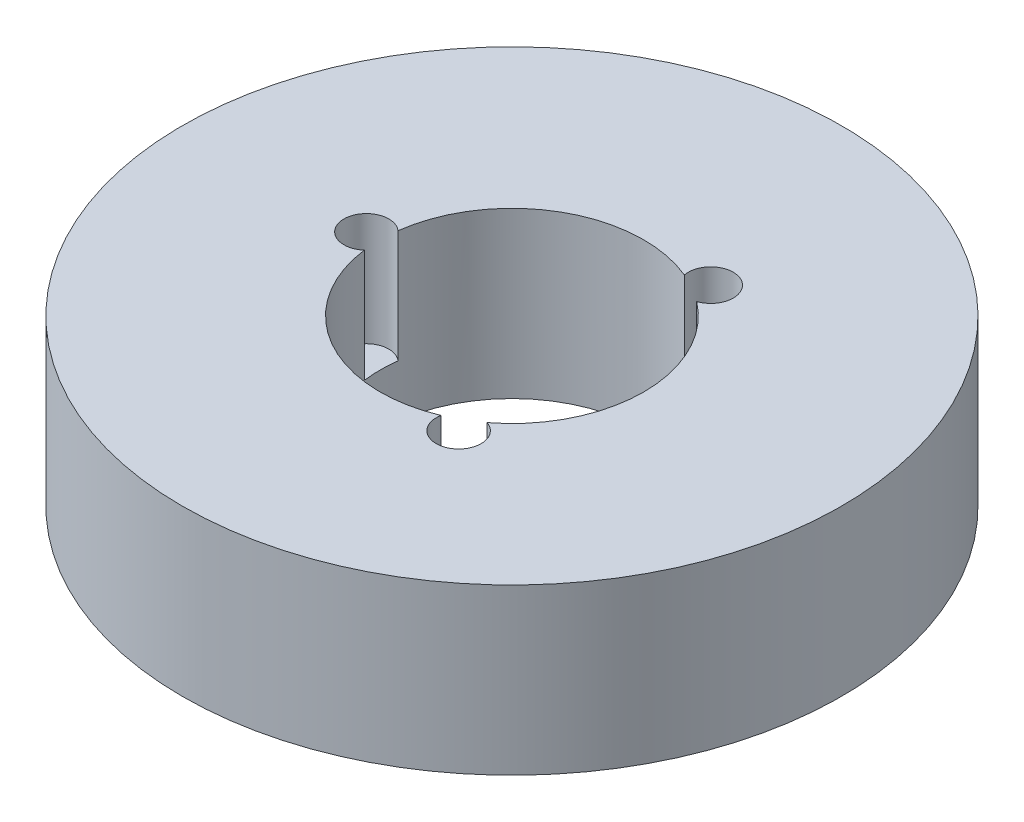
SolidWorks part; units mm, degrees
ref_plane "Front Plane" through (0, 0, 0) normal (0, 0, 1) x (1, 0, 0)
ref_plane "Top Plane" through (0, 0, 0) normal (0, 1, 0) x (1, 0, 0)
ref_plane "Right Plane" through (0, 0, 0) normal (1, 0, 0) x (0, 0, -1)
sketch "Sketch1" plane through (0, 0, 0) normal (0, 1, 0) x (1, 0, 0)
  circle A0 centre (0, 0) radius 50
  dimension "FLANGE_OD" = 100
extrude "Boss-Extrude1" add sketch "Sketch1" along normal blind 25
sketch "Sketch2" plane through (0, 0, 0) normal (0, 1, 0) x (1, 0, 0)
  circle A0 centre (0, 0) radius 20
  dimension "BORE_D" = 40
extrude "Cut-Extrude1" cut sketch "Sketch2" along normal through all
sketch "Sketch3" plane through (0, 25, 0) normal (0, 1, 0) x (1, 0, 0)
  circle A0 centre (0, 0) radius 22.0839 construction
  circle A1 centre (-22.0839, 0) radius 3.4063
  dimension "BOLT_D" = 6.8127
  dimension "BOLT_PCD" = 44.1678
extrude "Cut-Extrude2" cut sketch "Sketch3" against normal blind 17.1052
pattern_circular "CirPattern1" count 3 over 360 about axis through (0, 0, 0) along (0, 1, 0) of "Cut-Extrude2"
